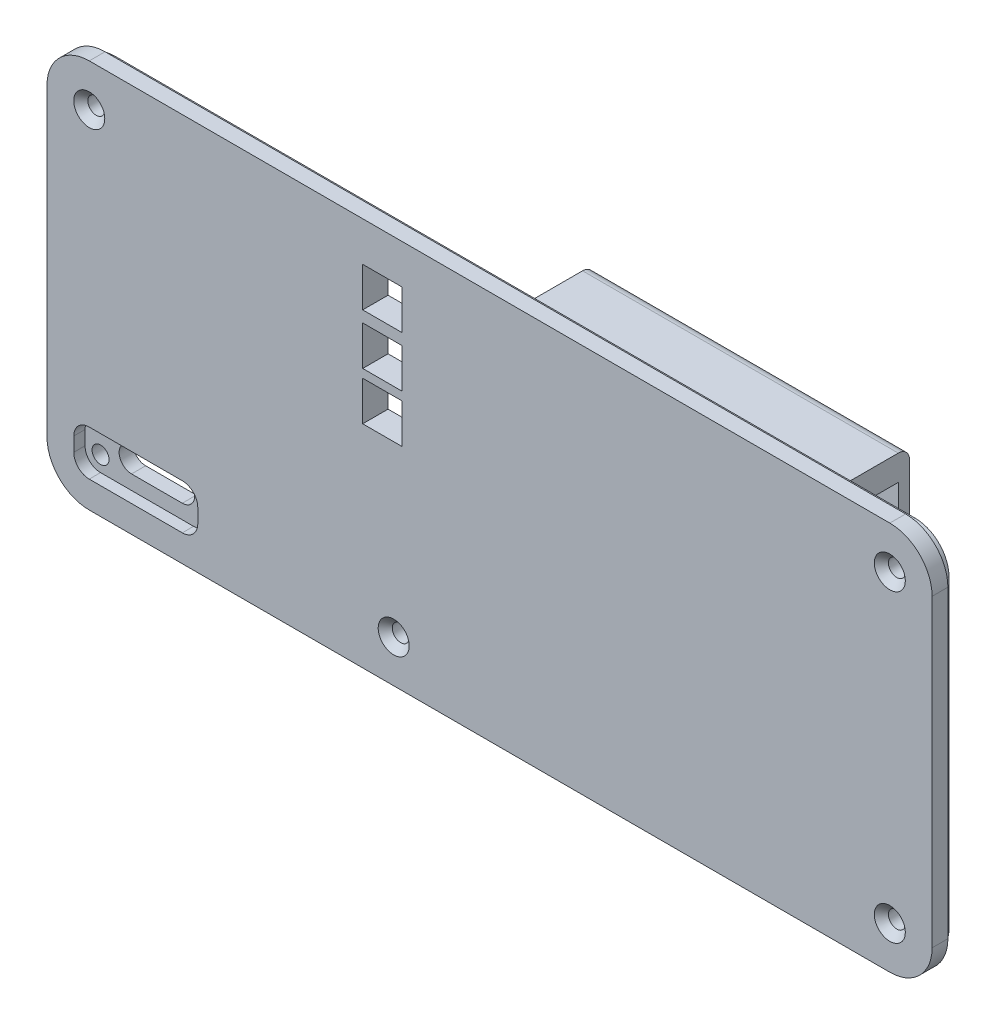
SolidWorks part; units mm, degrees
ref_plane "前视基准面" through (0, 0, 0) normal (0, 0, 1) x (1, 0, 0)
ref_plane "上视基准面" through (0, 0, 0) normal (0, 1, 0) x (1, 0, 0)
ref_plane "右视基准面" through (0, 0, 0) normal (1, 0, 0) x (0, 0, -1)
sketch "草图1" plane through (0, 0, 0) normal (0, 0, 1) x (1, 0, 0)
  line L1 (-71, -34.5) -> (71, -34.5)
  line L2 (-78.5, -27) -> (-78.5, 27)
  line L3 (-71, 34.5) -> (71, 34.5)
  line L4 (78.5, -27) -> (78.5, 27)
  line L5 (-78.5, -34.5) -> (78.5, 34.5) construction
  line L6 (-78.5, 34.5) -> (78.5, -34.5) construction
  line L7 (-71, -33) -> (71, -33)
  line L8 (-77, -27) -> (-77, 27)
  line L9 (-71, 33) -> (71, 33)
  line L10 (77, -27) -> (77, 27)
  line L11 (-77, -33) -> (77, 33) construction
  line L12 (-77, 33) -> (77, -33) construction
  arc A0 (-71, -34.5) -> (-78.5, -27) centre (-71, -27) cw
  arc A1 (71, -34.5) -> (78.5, -27) centre (71, -27) ccw
  arc A2 (78.5, 27) -> (71, 34.5) centre (71, 27) ccw
  arc A3 (-71, 34.5) -> (-78.5, 27) centre (-71, 27) ccw
  arc A4 (-71, -33) -> (-77, -27) centre (-71, -27) cw
  arc A5 (71, -33) -> (77, -27) centre (71, -27) ccw
  arc A6 (77, 27) -> (71, 33) centre (71, 27) ccw
  arc A7 (-71, 33) -> (-77, 27) centre (-71, 27) ccw
  point P0 (0, 0)
  point P18 (0, 0)
  dimension "D3" = 7.5
  dimension "D6" = 6
  dimension "D1" = 157
  dimension "D2" = 69
  dimension "D4" = 154
  dimension "D5" = 66
extrude "凸台-拉伸1" add sketch "草图1" against normal blind 2.8
extrude "凸台-拉伸2" add sketch "草图1<2>" against normal blind 4.5 contours L9 A7 L8 A4 L7 A5 L10 A6 region at (0, 0, 0)
sketch "草图1<2>" plane through (0, 0, 0) normal (0, 0, 1) x (1, 0, 0) same geometry as "草图1"
sketch "草图2" plane through (0, 0, 0) normal (0, 0, 1) x (1, 0, 0)
  line L0 (0, 0) -> (0, 34.5) construction
  line L1 (0, 0) -> (-78.5, 0) construction
  line L2 (-78.5, -27) -> (78.5, -27) construction
  line L3 (-44, -27) -> (-44, 34.5) construction
  line L4 (-71, -34.5) -> (71, -34.5)
  line L5 (78.5, -27) -> (78.5, 27)
  line L6 (71, 34.5) -> (-71, 34.5)
  line L7 (-78.5, 27) -> (-78.5, -27)
  line L8 (-71, -34.5) -> (71, -34.5) construction
  line L9 (78.5, -27) -> (78.5, 27) construction
  line L10 (71, 34.5) -> (-71, 34.5) construction
  line L11 (-78.5, 27) -> (-78.5, -27) construction
  circle A1 centre (-71, 27) radius 1.5
  circle A3 centre (-71, -27) radius 1.5
  arc A4 (-78.5, -27) -> (-71, -34.5) centre (-71, -27) ccw
  arc A5 (71, -34.5) -> (78.5, -27) centre (71, -27) ccw
  arc A6 (78.5, 27) -> (71, 34.5) centre (71, 27) ccw
  arc A7 (-71, 34.5) -> (-78.5, 27) centre (-71, 27) ccw
  arc A8 (-78.5, -27) -> (-71, -34.5) centre (-71, -27) ccw construction
  arc A9 (71, -34.5) -> (78.5, -27) centre (71, -27) ccw construction
  arc A10 (78.5, 27) -> (71, 34.5) centre (71, 27) ccw construction
  arc A11 (-71, 34.5) -> (-78.5, 27) centre (-71, 27) ccw construction
  circle A12 centre (71, 27) radius 1.5
  circle A13 centre (71, -27) radius 1.5
  circle A14 centre (-17, -27) radius 1.5
  point P16 (-44, -27)
  dimension "D2" = 3
  dimension "D4" = 27
  dimension "D1" = 0
extrude "切除-拉伸1" cut sketch "草图2" against normal blind 5
ref_plane "基准面1" through (-71, 0, 0) normal (1, 0, 0) x (0, 0, -1)
sketch "草图4" plane through (-71, 0, 0) normal (1, 0, 0) x (0, 0, -1)
  line L0 (2.8, 27) -> (0, 27) construction
  line L1 (2.75, 27) -> (0, 27)
  line L2 (0, 34.5) -> (0, 27) construction
  line L3 (0, 29.75) -> (0, 27)
  line L5 (-0.2, 27) -> (4.8, 27) construction
  line L6 (2.75, 27) -> (0, 29.75)
  point P5 (0, 29.75)
  point P6 (0, 29.75)
  point P7 (2.75, 27)
  dimension "D1" = 2.75
  dimension "D2" = 2.75
revolve "切除-旋转1" cut sketch "草图4" angle 360 about L5
pattern_linear "阵列(线性)1" count 2 spacing 142 along (1, 0, 0) count 2 spacing 54 along (0, -1, 0) of "切除-旋转1"
ref_plane "基准面2" through (-17, 0, 0) normal (1, 0, 0) x (0, 0, -1)
sketch "草图5" plane through (-17, 0, 0) normal (1, 0, 0) x (0, 0, -1)
  line L0 (2.8, -27) -> (0, -27) construction
  line L1 (2.75, -27) -> (0, -27)
  line L2 (0, 27) -> (0, -27) construction
  line L3 (2.75, -27) -> (0, -24.25)
  line L4 (0, -27) -> (0, -24.25)
  line L5 (-0.2, -27) -> (4.8, -27) construction
  point P2 (0, -24.25)
  point P3 (0, -24.25)
  point P6 (0, -27)
  point P7 (2.75, -27)
  dimension "D1" = 2.75
  dimension "D2" = 2.75
revolve "切除-旋转2" cut sketch "草图5" angle 360 about L5
sketch "草图6" plane through (0, 0, 0) normal (0, 0, 1) x (1, 0, 0)
  line L0 (0, 0) -> (-78.5, 0) construction
  line L1 (-78.5, 27) -> (-78.5, -27) construction
  line L2 (-71, -27) -> (-17, -27) construction
  line L3 (-17, -10.725) -> (-17, 10.725) construction
  line L4 (-61, -27) -> (-61, -34) construction
  line L5 (-67, -25) -> (-55, -25) construction
  line L6 (-61, -25) -> (-51.717, -25) construction
  line L7 (-67, -22) -> (-55, -22) construction
  line L8 (-67, -28) -> (-55, -28) construction
  line L9 (-71, -27) -> (-78.5, -27) construction
  line L10 (-52, -25) -> (-52, -34.5) construction
  line L12 (-71, -34.5) -> (71, -34.5) construction
  line L13 (-71, -27) -> (-71, -34) construction
  line L14 (-71, -10.725) -> (-71, 10.725) construction
  line L15 (-71, -29.75) -> (-52, -29.75) construction
  line L16 (-73.75, -27) -> (-73.75, -31.9547) construction
  line L17 (-62.75, -29.75) -> (-62.75, -21.2345) construction
  line L18 (-67, -22) -> (-73.75, -22) construction
  line L20 (-71, -21.75) -> (-54.5, -21.75)
  line L21 (-73.75, -24.5) -> (-73.75, -27)
  line L22 (-71, -29.75) -> (-54.5, -29.75)
  line L23 (-51.75, -24.5) -> (-51.75, -27)
  circle A0 centre (-71, -27) radius 1.5 construction
  circle A1 centre (-71, -27) radius 1.5 construction
  circle A2 centre (-71, -27) radius 2.75 construction
  circle A3 centre (-71, -27) radius 2.75 construction
  arc A4 (-67, -22) -> (-67, -28) centre (-67, -25) ccw construction
  arc A5 (-55, -28) -> (-55, -22) centre (-55, -25) ccw construction
  arc A6 (-71, -29.75) -> (-73.75, -27) centre (-71, -27) cw
  arc A7 (-54.5, -29.75) -> (-51.75, -27) centre (-54.5, -27) ccw
  arc A8 (-54.5, -21.75) -> (-51.75, -24.5) centre (-54.5, -24.5) cw
  arc A9 (-71, -21.75) -> (-73.75, -24.5) centre (-71, -24.5) ccw
  point P5 (-61, -27)
  point P13 (-61, -25)
  point P15 (-55, -25)
  point P18 (-67, -25)
  point P24 (-61, -25)
  point P29 (-52, -25)
  point P37 (-71, -29.75)
  point P39 (-73.75, -27)
  point P44 (-73.75, -29.75)
  point P46 (-73.75, -29.75)
  point P47 (-52, -29.75)
  point P48 (-51.75, -29.75)
  point P49 (-62.75, -29.75)
  point P54 (-73.75, -21.75)
  point P63 (-51.75, -29.75)
  point P68 (-73.75, -21.75)
  dimension "D5" = 3
  dimension "D9" = 2.75
  dimension "D1" = 10
  dimension "D2" = 2
  dimension "D3" = 6
  dimension "D4" = 6
  dimension "D6" = 22
  dimension "D7" = 11
  dimension "D8" = 8
extrude "切除-拉伸2" cut sketch "草图6" against normal blind 2
sketch "草图7" plane through (0, 0, -2) normal (0, 0, 1) x (1, 0, 0)
  line L0 (-71, -27) -> (-62.1885, -27) construction
  line L1 (-61, -27.983) -> (-61, -25.7259) construction
  line L2 (-61.1502, -25) -> (-57.3741, -25) construction
  line L3 (-65.5, -25) -> (-56.5, -25) construction
  line L4 (-65.5, -22.8) -> (-56.5, -22.8)
  line L5 (-65.5, -27.2) -> (-56.5, -27.2)
  circle A0 centre (-71, -27) radius 1.5 construction
  circle A1 centre (-71, -27) radius 1.5
  arc A2 (-65.5, -22.8) -> (-65.5, -27.2) centre (-65.5, -25) ccw
  arc A3 (-56.5, -27.2) -> (-56.5, -22.8) centre (-56.5, -25) ccw
  point P4 (-61, -27)
  point P7 (-61, -25)
  point P10 (-65.5, -25)
  point P12 (-56.5, -25)
  point P13 (-65.5, -25)
  point P14 (-61, -25)
  point P17 (-61, -25)
  dimension "D5" = 2.2
  dimension "D1" = 10
  dimension "D2" = 2
  dimension "D3" = 4.5
  dimension "D4" = 4.5
extrude "切除-拉伸3" cut sketch "草图7" against normal blind 3
sketch "草图8" plane through (0, 0, 0) normal (0, 0, 1) x (1, 0, 0)
  line L0 (-17, -27) -> (-17, 40.9028) construction
  line L1 (-19, 27) -> (-19, 23.8661) construction
  line L2 (-71, 27) -> (-38.5888, 27) construction
  line L9 (-22.5, 27.5) -> (-15.5, 27.5)
  line L10 (-22.5, 27.5) -> (-22.5, 20.5)
  line L14 (-22.5, 20.5) -> (-15.5, 20.5)
  line L15 (-15.5, 27.5) -> (-15.5, 20.5)
  line L20 (-22.5, 27.5) -> (-15.5, 20.5) construction
  line L21 (-22.5, 20.5) -> (-15.5, 27.5) construction
  line L22 (-22.5, 18.5) -> (-15.5, 18.5)
  line L23 (-22.5, 18.5) -> (-22.5, 11.5)
  line L24 (-22.5, 11.5) -> (-15.5, 11.5)
  line L25 (-15.5, 18.5) -> (-15.5, 11.5)
  line L26 (-22.5, 18.5) -> (-15.5, 11.5) construction
  line L27 (-22.5, 11.5) -> (-15.5, 18.5) construction
  line L28 (-22.5, 10) -> (-15.5, 10)
  line L29 (-22.5, 10) -> (-22.5, 3)
  line L30 (-22.5, 3) -> (-15.5, 3)
  line L31 (-15.5, 10) -> (-15.5, 3)
  line L32 (-22.5, 10) -> (-15.5, 3) construction
  line L33 (-22.5, 3) -> (-15.5, 10) construction
  circle A0 centre (-71, 27) radius 1.5 construction
  circle A1 centre (-71, 27) radius 1.5 construction
  circle A2 centre (-17, -27) radius 1.5 construction
  circle A3 centre (-17, -27) radius 1.5 construction
  point P6 (-19, 27)
  point P11 (-17, 27)
  point P14 (-19, 24)
  point P15 (-19, 24)
  point P20 (-19, 6.5)
  point P21 (-19, 15)
  point P22 (-19, 15)
  point P27 (-19, 6.5)
  dimension "D1" = 2
  dimension "D2" = 3
  dimension "D3" = 7
  dimension "D4" = 7
  dimension "D5" = 9
  dimension "D6" = 8.5
  dimension "D7" = 7
  dimension "D8" = 7
  dimension "D9" = 7
  dimension "D10" = 7
extrude "切除-拉伸4" cut sketch "草图8" against normal blind 5
ref_plane "基准面3" through (55, 0, 0) normal (1, 0, 0) x (0, 0, -1)
sketch "草图9" plane through (55, 0, 0) normal (1, 0, 0) x (0, 0, -1)
  line L0 (0, -27) -> (0, 27) construction
  line L1 (0, -23.5) -> (0, 0) construction
  line L2 (0, 0) -> (0, -24)
  line L3 (0, -24) -> (8.5695, -24) construction
  line L6 (0, -28.5) -> (10.7376, -28.5) construction
  line L7 (4.5, -24) -> (17.5, -24)
  line L11 (0, 0) -> (28.8012, 0) construction
  line L15 (4.5, -33) -> (4.5, -27) construction
  line L16 (4.5, -28.5) -> (19.5, -28.5)
  line L17 (17.5, 24) -> (17.5, -24)
  line L18 (19.5, 28.5) -> (19.5, -28.5)
  line L19 (4.5, -24) -> (4.5, -28.5)
  line L20 (4.5, 28.5) -> (19.5, 28.5)
  line L21 (4.5, 24) -> (4.5, 28.5)
  line L22 (4.5, 24) -> (17.5, 24)
  point P10 (19.5, 0)
  point P11 (0, -28.5)
  point P19 (4.5, -28.5)
  point P23 (19.5, 0)
  point P24 (17.5, 0)
  point P26 (17.5, 0)
  dimension "D1" = 24
  dimension "D2" = 4.5
  dimension "D3" = 13
  dimension "D5" = 15
extrude "凸台-拉伸3" add sketch "草图9" against normal blind 56 contours L7 L21 L22 region at (55, -24.5894, -11)
fillet "圆角1" radius 2 2 edges at (27, -28.5, -19.5) (27, 28.5, -19.5)
